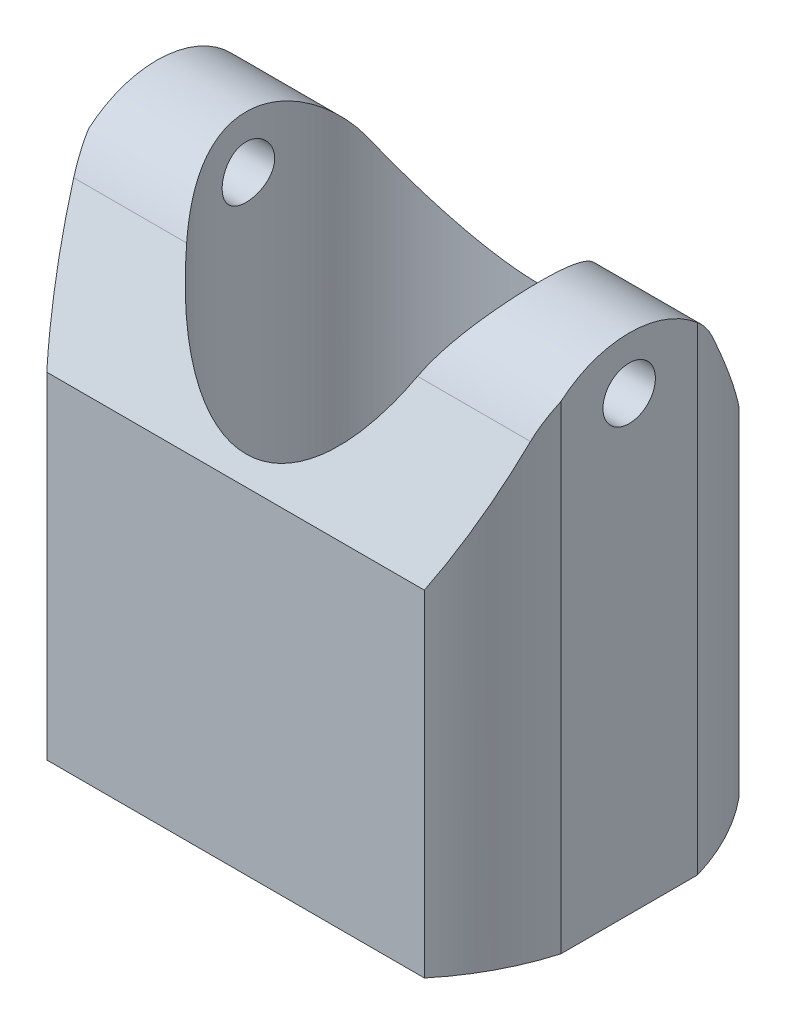
SolidWorks part; units mm, degrees
ref_plane "Front Plane" through (0, 0, 0) normal (0, 0, 1) x (1, 0, 0)
ref_plane "Top Plane" through (0, 0, 0) normal (0, 1, 0) x (1, 0, 0)
ref_plane "Right Plane" through (0, 0, 0) normal (1, 0, 0) x (0, 0, -1)
sketch "Sketch1" plane through (0, 0, 0) normal (0, 1, 0) x (1, 0, 0)
  line L0 (-22.5, -15) -> (22.5, -15)
  line L7 (-22.5, -15) -> (-22.5, 15)
  line L8 (-22.5, 15) -> (22.5, 15)
  line L9 (22.5, -15) -> (22.5, 15)
  line L10 (-22.5, -15) -> (22.5, 15) construction
  line L11 (-22.5, 15) -> (22.5, -15) construction
  line L12 (-15.5, -9) -> (15.5, -9) construction
  line L13 (-15.5, -9) -> (-15.5, 9) construction
  line L14 (-15.5, 9) -> (15.5, 9) construction
  line L15 (15.5, -9) -> (15.5, 9) construction
  line L16 (-15.5, -9) -> (15.5, 9) construction
  line L17 (-15.5, 9) -> (15.5, -9) construction
  circle A2 centre (0, 0) radius 14
  circle A3 centre (-15.5, 9) radius 2.5
  circle A4 centre (15.5, 9) radius 2.5
  circle A5 centre (15.5, -9) radius 2.5
  circle A6 centre (-15.5, -9) radius 2.5
  circle A7 centre (0, 0) radius 23.4201
  point P0 (0, 0)
  point P8 (0, 0)
  point P24 (22.5, 6.5)
  point P25 (22.5, -6.5)
  dimension "D1" = 28
  dimension "D8" = 5
  dimension "D4" = 30
  dimension "D5" = 45
  dimension "D6" = 31
  dimension "D7" = 18
  dimension "D9" = 13
extrude "Boss-Extrude1" add sketch "Sketch1" along normal blind 32 contours L0 A7 L9 L8 L7 A6 A5 A4 A3 A2 region at (-20.2067, 0, 10.7307)
ref_plane "Plane1" through (22.5, 0, 0) normal (1, 0, 0) x (0, 0, -1)
sketch "Sketch3" plane through (22.5, 0, 0) normal (1, 0, 0) x (0, 0, -1)
  line L0 (-15, 32) -> (15, 32)
  line L1 (15, 32) -> (15, 0) construction
  line L2 (15, 32) -> (0, 57.9808)
  line L3 (0, 57.9808) -> (-15, 32)
extrude "Boss-Extrude2" add sketch "Sketch3" against normal blind 45
sketch "Sketch4" plane through (0, 0, 0) normal (0, -1, 0) x (1, 0, 0)
  circle A0 centre (0, 0) radius 23.4201
  circle A1 centre (0, 0) radius 49.3971
  circle A2 centre (0, 0) radius 14
  circle M7 centre (0, 0) radius 14
  arc M9 (-17.9861, 15) -> (-22.5, 6.5) centre (0, 0) ccw
  arc M11 (-22.5, -6.5) -> (-17.9861, -15) centre (0, 0) ccw
  arc M13 (17.9861, -15) -> (22.5, -6.5) centre (0, 0) ccw
  arc M15 (22.5, 6.5) -> (17.9861, 15) centre (0, 0) ccw
extrude "Cut-Extrude1" cut sketch "Sketch4" against normal blind 90 contours M7 | A1 A0 M13 M11 M9 M15 region at (-47.9999, 0, 0) region at (0, 0, 0)
fillet "Fillet1" radius 10 2 edges at (-18.25, 57.9808, 0) (18.25, 57.9808, 0)
sketch "Sketch6" plane through (-22.5, 0, 0) normal (-1, 0, 0) x (0, 0, 1)
  circle A0 centre (0, 43) radius 2.5
  dimension "D1" = 5
  dimension "D2" = 43
extrude "Cut-Extrude2" cut sketch "Sketch6" against normal blind 90
